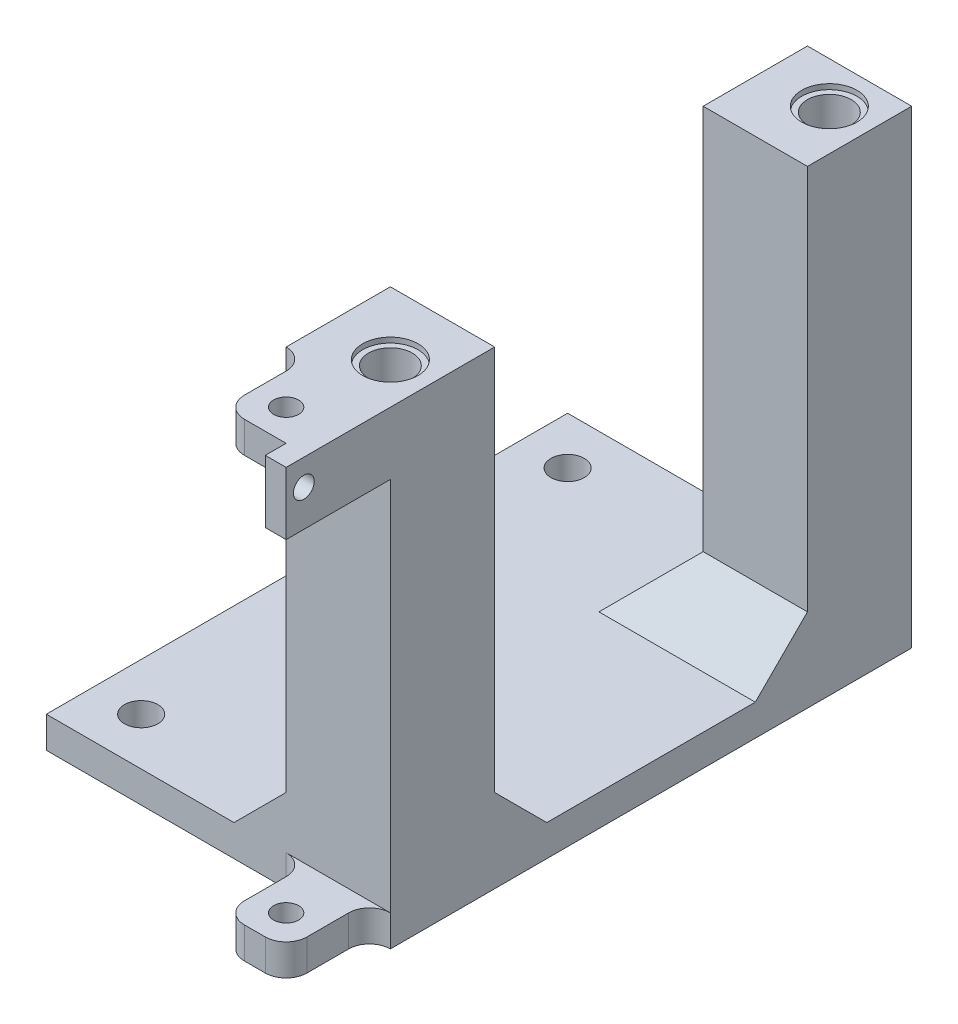
SolidWorks part; units mm, degrees
ref_plane "Front Plane" through (0, 0, 0) normal (0, 0, 1) x (1, 0, 0)
ref_plane "Top Plane" through (0, 0, 0) normal (0, 1, 0) x (1, 0, 0)
ref_plane "Right Plane" through (0, 0, 0) normal (1, 0, 0) x (0, 0, -1)
sketch "Sketch1" plane through (0, 0, 0) normal (0, 1, 0) x (1, 0, 0)
  line L1 (-6.5124, 9.686) -> (1.4876, 9.686)
  line L2 (-6.5124, 9.686) -> (-6.5124, -40.314)
  line L3 (-6.5124, -40.314) -> (1.4876, -40.314)
  line L4 (1.4876, 9.686) -> (1.4876, -40.314)
  line L5 (1.4876, 9.686) -> (26.4876, 9.686)
  line L6 (1.4876, 9.686) -> (1.4876, -40.314)
  line L7 (1.4876, -40.314) -> (26.4876, -40.314)
  line L8 (26.4876, 9.686) -> (26.4876, -40.314)
  circle A0 centre (-1.9624, -35.764) radius 1.6
  circle A1 centre (-1.9624, 5.136) radius 1.6
  dimension "D4" = 3.2
  dimension "D5" = 3.2
  dimension "D6" = 4.55
  dimension "D7" = 4.55
  dimension "D8" = 4.55
  dimension "D9" = 4.55
  dimension "D1" = 8
  dimension "D2" = 50
  dimension "D3" = 25
extrude "Boss-Extrude1" add sketch "Sketch1" along normal blind 3 contours A1 | A0 | L5 L8 L7 L3 L2 L1
sketch "Sketch2" plane through (0, 3, 0) normal (0, 1, 0) x (1, 0, 0)
  line L1 (26.4876, -40.314) -> (16.4876, -40.314)
  line L2 (26.4876, -40.314) -> (26.4876, -30.314)
  line L3 (26.4876, -30.314) -> (16.4876, -30.314)
  line L4 (16.4876, -40.314) -> (16.4876, -30.314)
  line L5 (26.4876, 9.686) -> (16.4876, 9.686)
  line L6 (26.4876, 9.686) -> (26.4876, -0.314)
  line L7 (26.4876, -0.314) -> (16.4876, -0.314)
  line L8 (16.4876, 9.686) -> (16.4876, -0.314)
  dimension "D1" = 10
  dimension "D2" = 10
  dimension "D3" = 10
  dimension "D4" = 10
extrude "Boss-Extrude2" add sketch "Sketch2" along normal blind 42
chamfer "Chamfer1" distance 5 angle 45 4 edges at (16.4876, 3, -4.686) (21.4876, 3, 0.314) (16.4876, 3, 35.314) (21.4876, 3, 30.314)
ref_plane "Plane1" through (0, 45, 0) normal (0, 1, 0) x (1, 0, 0)
sketch "Sketch3" plane through (0, 45, 0) normal (0, 1, 0) x (1, 0, 0)
  line L0 (26.4876, -40.314) -> (26.4876, -30.314) construction
  line L1 (16.4876, -40.314) -> (26.4876, -40.314) construction
  line L2 (26.4876, -0.314) -> (26.4876, 9.686) construction
  line L3 (26.4876, 9.686) -> (16.4876, 9.686) construction
  circle A0 centre (22.5376, -36.364) radius 2.1
  circle A1 centre (22.5376, 5.736) radius 2.1
  dimension "D1" = 4.2
  dimension "D3" = 3.95
  dimension "D4" = 4.2
  dimension "D6" = 3.95
  dimension "D2" = 3.95
  dimension "D5" = 3.95
extrude "Cut-Extrude1" cut sketch "Sketch3" against normal blind 52
sketch "Sketch4" plane through (0, 45, 0) normal (0, 1, 0) x (1, 0, 0)
  circle A0 centre (22.5376, -36.364) radius 2.65
  circle A1 centre (22.5376, 5.736) radius 2.65
  dimension "D1" = 5.3
  dimension "D2" = 5.3
extrude "Cut-Extrude2" cut sketch "Sketch4" against normal blind 0.5
ref_plane "Plane2" through (0, 22.5, 0) normal (0, -1, 0) x (-1, 0, 0)
mirror "Mirror1" about plane through (0, 22.5, 0) normal (0, -1, 0) of "Cut-Extrude2"
sketch "Sketch5" plane through (0, 0, -9.686) normal (0, 0, -1) x (-1, 0, 0)
  line L0 (-22.4876, 36.5) -> (-17.9876, 36.5) construction
  line L1 (-18.2876, 36.2) -> (-22.2399, 36.2)
  line L2 (-18.2876, 36.2) -> (-18.2876, 31.6868)
  line L3 (-18.2876, 31.6868) -> (-22.2399, 31.6868)
  line L4 (-22.2399, 36.2) -> (-22.2399, 31.6868)
  line L5 (-17.9876, 32.25) -> (-17.9876, 37) construction
  dimension "D1" = 0.3
  dimension "D2" = 0.3
sketch "Sketch11" plane through (0, 0, 40.314) normal (0, 0, 1) x (1, 0, 0)
  line L0 (16.4876, 45) -> (26.4876, 45) construction
  line L1 (18.4876, 45) -> (24.4876, 45)
  line L2 (18.4876, 45) -> (18.4876, 42)
  line L3 (18.4876, 42) -> (24.4876, 42)
  line L4 (24.4876, 45) -> (24.4876, 42)
  line L5 (-6.5124, 0) -> (26.4876, 0) construction
  line L6 (18.4876, 0) -> (24.4876, 0)
  line L7 (18.4876, 0) -> (18.4876, 3)
  line L8 (18.4876, 3) -> (24.4876, 3)
  line L9 (24.4876, 0) -> (24.4876, 3)
  line L10 (21.4876, 8) -> (21.4876, 0) construction
  line L11 (21.4876, 8) -> (21.4876, 45) construction
  line L13 (-6.5124, 3) -> (11.4876, 3) construction
  line L14 (16.4876, 8) -> (26.4876, 8) construction
  line L15 (26.4876, 8) -> (39.3241, 4.4212) construction
  line L16 (39.3241, 4.4212) -> (39.5028, 4.4212) construction
  dimension "D1" = 3
  dimension "D2" = 3
  dimension "D3" = 3
  dimension "D4" = 3
  dimension "D5" = 3
extrude "Boss-Extrude7" add sketch "Sketch11" along normal blind 8
sketch "Sketch12" plane through (0, 0, 0) normal (0, -1, 0) x (1, 0, 0)
  line L0 (24.4876, 48.314) -> (24.4876, 40.314) construction
  line L1 (18.4876, 48.314) -> (24.4876, 48.314) construction
  line L2 (18.4876, 48.314) -> (18.4876, 42.314) construction
  line L3 (18.4876, 42.314) -> (24.4876, 42.314) construction
  line L4 (24.4876, 48.314) -> (24.4876, 42.314) construction
  line L5 (18.4876, 48.314) -> (24.4876, 42.314) construction
  line L6 (18.4876, 42.314) -> (24.4876, 48.314) construction
  circle A0 centre (21.4876, 45.314) radius 1.2
  point P494 (21.4876, 45.314)
  dimension "D1" = 2.4
  dimension "D2" = 6
extrude "Cut-Extrude5" cut sketch "Sketch12" against normal through all
fillet "Fillet1" radius 2 6 edges at (18.4876, 43.5, 40.314) (18.4876, 43.5, 48.314) (24.4876, 1.5, 48.314) (18.4876, 1.5, 48.314) (18.4876, 1.5, 40.314) (24.4876, 1.5, 40.314)
sketch "Sketch13" plane through (0, 0, 40.314) normal (0, 0, 1) x (1, 0, 0)
  line L0 (26.4876, 45) -> (26.4876, 3) construction
  line L1 (24.4876, 45) -> (26.4876, 45)
  line L2 (24.4876, 45) -> (24.4876, 42)
  line L3 (24.4876, 42) -> (26.4876, 42)
  line L4 (26.4876, 45) -> (26.4876, 42)
  line L5 (16.4876, 42) -> (24.4876, 42) construction
extrude "Boss-Extrude8" add sketch "Sketch13" along normal blind 10
sketch "Sketch14" plane through (0, 42, 0) normal (0, -1, 0) x (1, 0, 0)
  line L0 (16.4876, 40.314) -> (26.4876, 40.314) construction
  line L1 (26.4876, 50.314) -> (24.4876, 50.314)
  line L2 (26.4876, 50.314) -> (26.4876, 40.314)
  line L3 (26.4876, 40.314) -> (24.4876, 40.314)
  line L4 (24.4876, 50.314) -> (24.4876, 40.314)
  line L5 (24.4876, 50.314) -> (24.4876, 48.314) construction
extrude "Boss-Extrude9" add sketch "Sketch14" along normal blind 3
sketch "Sketch15" plane through (26.4876, 0, 0) normal (1, 0, 0) x (0, 0, -1)
  circle A0 centre (-48.614, 42.5) radius 1
  point P2 (0, 0)
  point P4 (0, 0)
  dimension "D1" = 2
extrude "Cut-Extrude6" cut sketch "Sketch15" against normal blind 3
